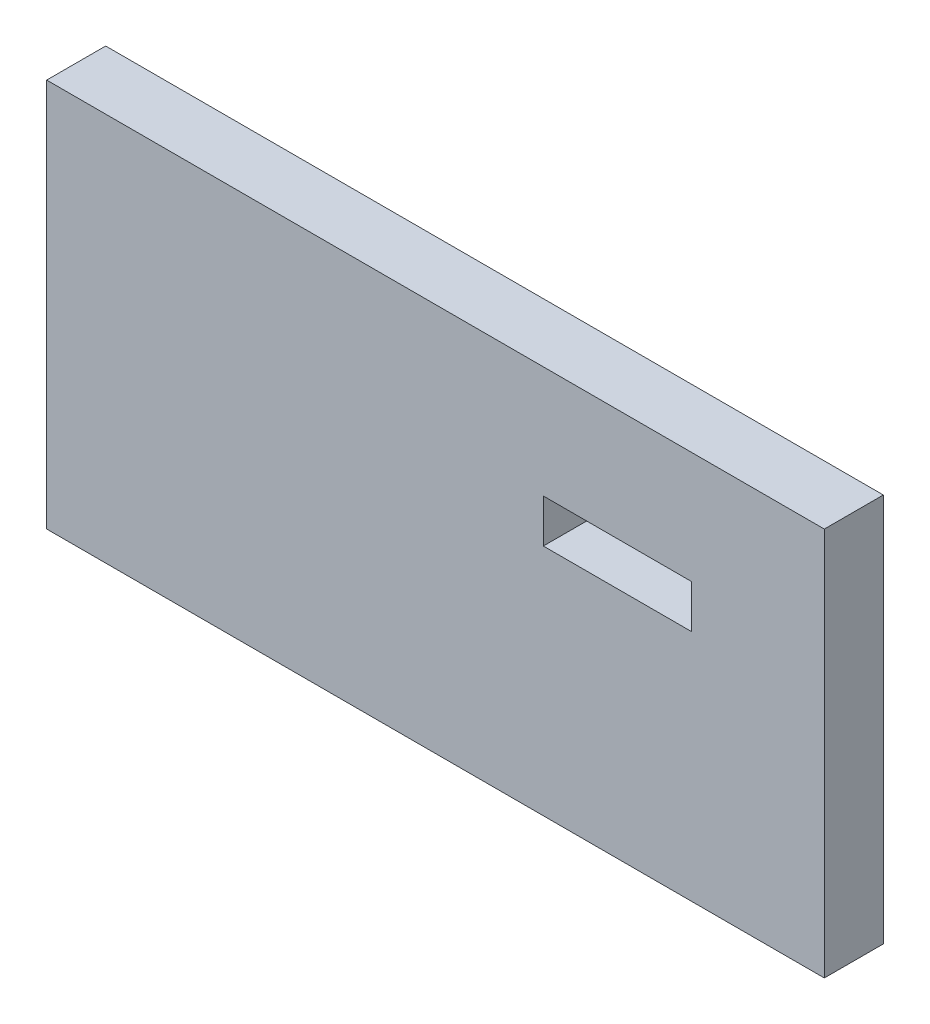
SolidWorks part; units mm, degrees
ref_plane "Front Plane" through (0, 0, 0) normal (0, 0, 1) x (1, 0, 0)
ref_plane "Top Plane" through (0, 0, 0) normal (0, 1, 0) x (1, 0, 0)
ref_plane "Right Plane" through (0, 0, 0) normal (1, 0, 0) x (0, 0, -1)
sketch "Sketch1" plane through (0, 0, 0) normal (0, 0, 1) x (1, 0, 0)
  line L1 (0, 0) -> (131.7823, 0)
  line L2 (0, 0) -> (0, 65.8912)
  line L3 (0, 65.8912) -> (131.7823, 65.8912)
  line L4 (131.7823, 0) -> (131.7823, 65.8912)
  line L5 (84.1666, 46.9356) -> (109.2895, 46.9356)
  line L6 (84.1666, 46.9356) -> (84.1666, 39.5891)
  line L7 (84.1666, 39.5891) -> (109.2895, 39.5891)
  line L8 (109.2895, 46.9356) -> (109.2895, 39.5891)
extrude "Boss-Extrude1" add sketch "Sketch1" along normal blind 10
